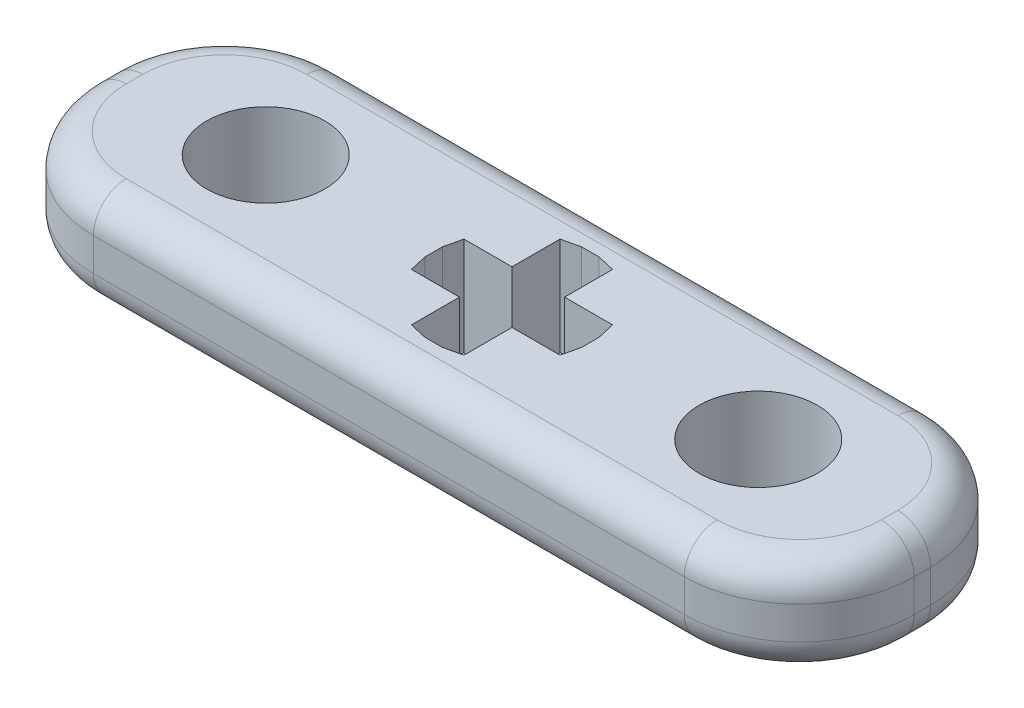
SolidWorks part; units mm, degrees
ref_plane "Front Plane" through (0, 0, 0) normal (0, 0, 1) x (1, 0, 0)
ref_plane "Top Plane" through (0, 0, 0) normal (0, 1, 0) x (1, 0, 0)
ref_plane "Right Plane" through (0, 0, 0) normal (1, 0, 0) x (0, 0, -1)
sketch "Sketch1" plane through (0, 0, 0) normal (0, 1, 0) x (1, 0, 0)
  line L0 (-0.8, 0.8) -> (-0.8, 2.2627)
  line L1 (-12.5, -3.75) -> (12.5, -3.75)
  line L2 (-12.5, -3.75) -> (-12.5, 3.75)
  line L3 (-12.5, 3.75) -> (12.5, 3.75)
  line L4 (12.5, -3.75) -> (12.5, 3.75)
  line L5 (-12.5, -3.75) -> (12.5, 3.75) construction
  line L6 (-12.5, 3.75) -> (12.5, -3.75) construction
  line L8 (-5, -3.75) -> (-5, 3.75)
  line L10 (5, -3.75) -> (5, 3.75)
  line L11 (3.5787, -3.75) -> (6.4358, 3.75) construction
  line L12 (3.5642, 3.75) -> (6.4213, -3.75) construction
  line L13 (-0.8, 2.2627) -> (-0.2701, 2.3847)
  line L14 (-0.2701, 2.3847) -> (0.2701, 2.3847)
  line L15 (0.2701, 2.3847) -> (0.8, 2.2627)
  line L16 (0.8, 2.2627) -> (0.8, 0.8)
  line L17 (0.8, 0.8) -> (2.2627, 0.8)
  line L18 (2.2627, 0.8) -> (2.3847, 0.2701)
  line L19 (2.3847, 0.2701) -> (2.3847, -0.2701)
  line L20 (2.3847, -0.2701) -> (2.2627, -0.8)
  line L21 (2.2627, -0.8) -> (0.8, -0.8)
  line L22 (0.8, -0.8) -> (0.8, -2.2627)
  line L23 (0.8, -2.2627) -> (0.2701, -2.3847)
  line L24 (0.2701, -2.3847) -> (-0.2701, -2.3847)
  line L25 (-0.2701, -2.3847) -> (-0.8, -2.2627)
  line L26 (-0.8, -2.2627) -> (-0.8, -0.8)
  line L27 (-0.8, -0.8) -> (-2.2627, -0.8)
  line L28 (-2.2627, -0.8) -> (-2.3847, -0.2701)
  line L29 (-2.3847, -0.2701) -> (-2.3847, 0.2701)
  line L30 (-2.3847, 0.2701) -> (-2.2627, 0.8)
  line L31 (-2.2627, 0.8) -> (-0.8, 0.8)
  line L32 (-5, 3.75) -> (5, 3.75) construction
  circle A1 centre (0, 0) radius 3
  point P2 (0, 3.75)
  dimension "D1" = 6
  dimension "D3" = 10
  dimension "D4" = 25
  dimension "D5" = 7.5
extrude "Boss-Extrude1" add sketch "Sketch1" along normal blind 3 contours L1 L10 L3 L8 | L3 L10 L8 | L1 L8 L3 L2 | L10 L1 L8 | L2 L1 L4 L3 | L0 L13 L14 L15 L16 L17 L18 L19 L20 L21 L22 L23 L24 L25 L26 L27 L28 L29 L30 L31 region at (-8.75, 0, 0) region at (-4.875, 0, 0)
fillet "Fillet4" radius 3.5 4 edges at (12.5, 1.5, -3.75) (12.5, 1.5, 3.75) (-12.5, 1.5, 3.75) (-12.5, 1.5, -3.75)
hole_wizard "M3 Clearance Hole1" positions "Sketch2" profile "Sketch3" hole size "M3" standard "ANSI Metric" end condition through all
sketch "Sketch2" plane through (0, 0, 0) normal (0, 1, 0) x (1, 0, 0)
  line L0 (-7.5, 0) -> (7.5, 0)
  line L2 (12.5, -0.25) -> (12.5, 0.25) construction
  point P0 (-7.5, 0)
  point P2 (7.5, 0)
  point P26 (0, 0)
  dimension "D1" = 5
sketch "Sketch3" plane through (-7.5, 0, 0) normal (1, 0, 0) x (0, 0, -1)
  line L0 (0, 0) -> (0, 3)
  line L1 (0, 3) -> (1.8, 3)
  line L2 (1.8, 3) -> (1.8, 0)
  line L5 (1.8, 0) -> (0, 0)
  line L11 (0, -6.35) -> (0, 107.95) construction
  dimension "Thru Hole Dia." = 3.6
  dimension "Thru Hole Depth" = 3
fillet "Fillet6" radius 1 16 edges at (-11.4749, 3, 2.7249) (0, 3, 3.75) (11.4749, 3, 2.7249) (11.4749, 3, -2.7249) (0, 3, -3.75) (-11.4749, 3, -2.7249) (-11.4749, 0, 2.7249) (0, 0, 3.75) (11.4749, 0, 2.7249) (11.4749, 0, -2.7249) (0, 0, -3.75) (-11.4749, 0, -2.7249) (12.5, 3, 0) (12.5, 0, 0) (-12.5, 3, 0) (-12.5, 0, 0)
